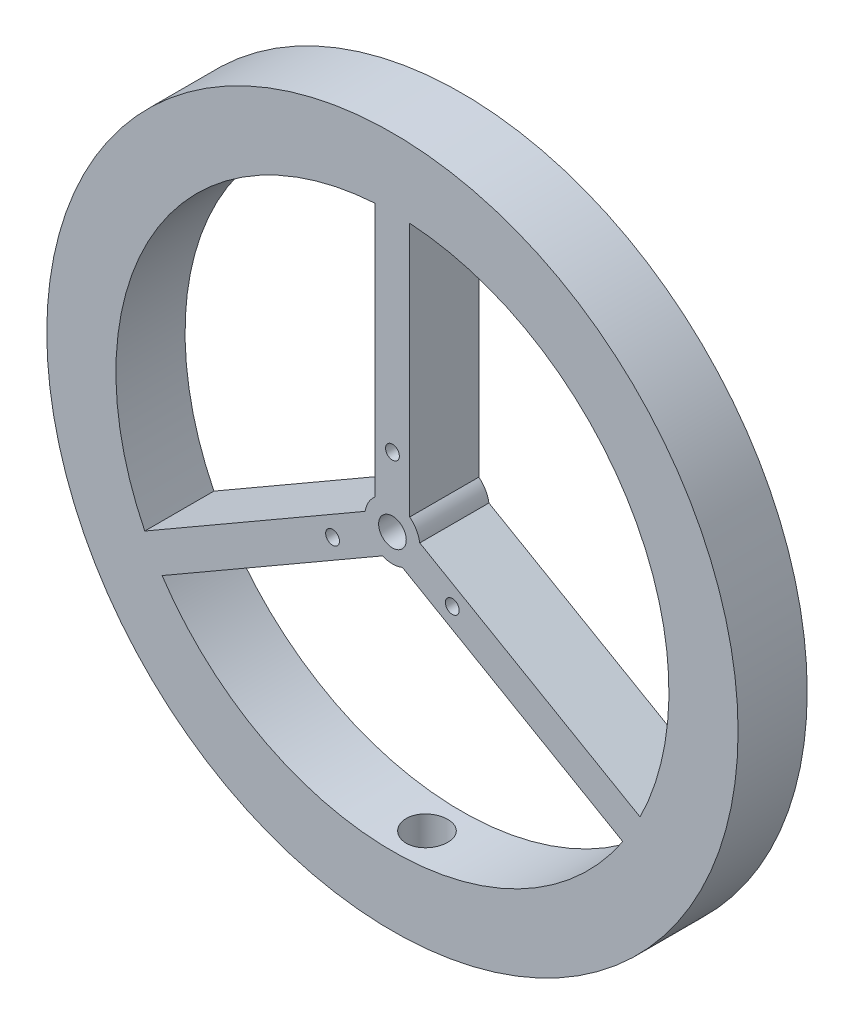
SolidWorks part; units mm, degrees
ref_plane "Front Plane" through (0, 0, 0) normal (0, 0, 1) x (1, 0, 0)
ref_plane "Top Plane" through (0, 0, 0) normal (0, 1, 0) x (1, 0, 0)
ref_plane "Right Plane" through (0, 0, 0) normal (1, 0, 0) x (0, 0, -1)
sketch "Sketch1" plane through (0, 0, 0) normal (0, 0, 1) x (1, 0, 0)
  line L1 (0, 10) -> (0, 0) construction
  line L2 (0, 0) -> (8.6603, -5) construction
  line L3 (0, 0) -> (-8.6603, -5) construction
  circle A1 centre (0, 10) radius 1
  circle A4 centre (0, 0) radius 2
  circle A5 centre (-8.6603, -5) radius 1
  circle A6 centre (8.6603, -5) radius 1
  dimension "D1" = 4
  dimension "D2" = 2
  dimension "D3" = 10
sketch "Sketch2" plane through (0, 0, 0) normal (0, 0, 1) x (1, 0, 0)
  line L2 (2.5, 39.9218) -> (2.5, 3.1225)
  line L4 (-2.5, 39.9218) -> (-2.5, 3.1225)
  line L5 (3.9542, 0.6038) -> (35.8233, -17.7958)
  line L7 (33.3233, -22.126) -> (1.4542, -3.7263)
  line L8 (0, 0) -> (0, 113.6326) construction
  line L9 (0, 0) -> (59.8703, -34.5661) construction
  line L10 (0, 0) -> (-67.4581, -38.947) construction
  line L12 (-1.4542, -3.7263) -> (-33.3233, -22.126)
  line L14 (-35.8233, -17.7958) -> (-3.9542, 0.6038)
  arc A0 (-2.5, 39.9218) -> (-35.8233, -17.7958) centre (0, 0) ccw
  circle A1 centre (0, 0) radius 50
  arc A2 (-1.4542, -3.7263) -> (1.4542, -3.7263) centre (0, 0) ccw
  arc A3 (-33.3233, -22.126) -> (33.3233, -22.126) centre (0, 0) ccw
  arc A4 (35.8233, -17.7958) -> (2.5, 39.9218) centre (0, 0) ccw
  arc A5 (-2.5, 3.1225) -> (-3.9542, 0.6038) centre (0, 0) ccw
  arc A6 (3.9542, 0.6038) -> (2.5, 3.1225) centre (0, 0) ccw
  dimension "D1" = 100
  dimension "D2" = 80
  dimension "D3" = 8
extrude "Boss-Extrude1" add sketch "Sketch2" along normal blind 10
extrude "Cut-Extrude2" cut sketch "Sketch1" along normal through all
sketch "Sketch3" plane through (0, 0, 0) normal (0, 1, 0) x (1, 0, 0)
  circle A0 centre (0, -5) radius 3
  dimension "D1" = 6
  dimension "D2" = 5
extrude "Cut-Extrude3" cut sketch "Sketch3" against normal through all from offset 10 offset against normal yes
